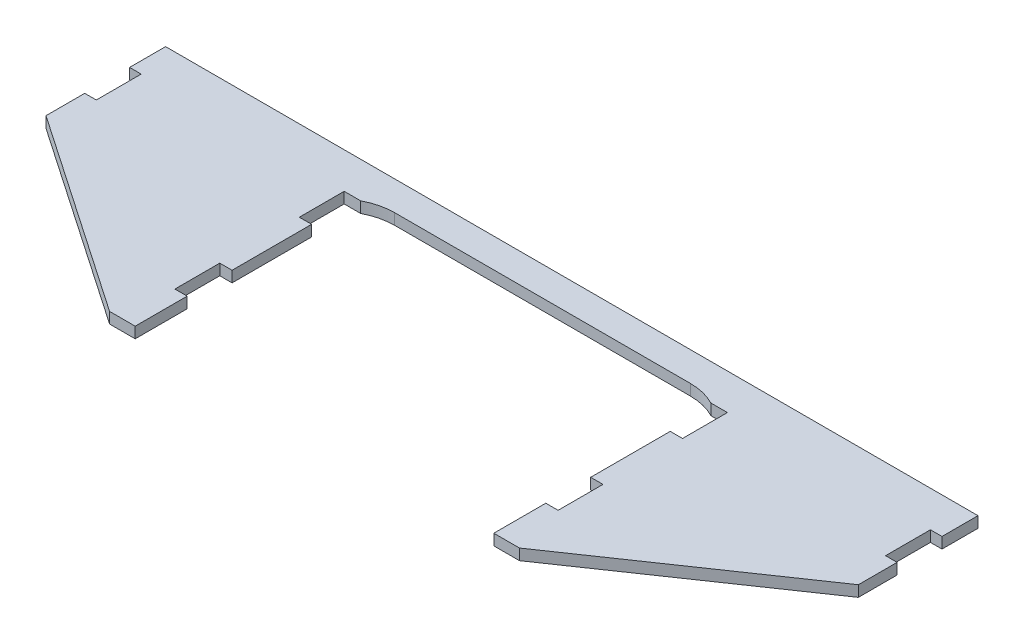
SolidWorks part; units mm, degrees
material "Plain Carbon Steel"
ref_plane "Front Plane" through (0, 0, 0) normal (0, 0, 1) x (1, 0, 0)
ref_plane "Top Plane" through (0, 0, 0) normal (0, 1, 0) x (1, 0, 0)
ref_plane "Right Plane" through (0, 0, 0) normal (1, 0, 0) x (0, 0, -1)
sketch "Sketch1" plane through (0, 0, 0) normal (0, 1, 0) x (1, 0, 0)
  line L0 (0, 25.4) -> (0, 0) construction
  line L1 (-177.8, 25.4) -> (177.8, 25.4)
  line L2 (-177.8, 25.4) -> (-177.8, -25.4)
  line L3 (-177.8, -25.4) -> (177.8, -25.4)
  line L4 (177.8, 25.4) -> (177.8, -25.4)
  line L5 (0, 0) -> (177.8, 0) construction
  dimension "D1" = 177.8
  dimension "D2" = 25.4
extrude "Boss-Extrude1" add sketch "Sketch1" along normal blind 4.7625
sketch "Sketch2" plane through (0, 4.7625, 0) normal (0, 1, 0) x (1, 0, 0)
  line L0 (177.8, -25.4) -> (88.9, -86.2204)
  line L1 (88.9, -86.2204) -> (76.2, -86.2204)
  line L2 (76.2, -86.2204) -> (76.2, -25.4)
  line L3 (-177.8, -25.4) -> (177.8, -25.4) construction
  line L4 (76.2, -25.4) -> (177.8, -25.4)
  line L5 (-177.8, -25.4) -> (-88.9, -86.2204)
  line L6 (-88.9, -86.2204) -> (-76.2, -86.2204)
  line L7 (-76.2, -86.2204) -> (-76.2, -25.4)
  line L8 (-76.2, -25.4) -> (-177.8, -25.4)
  line L9 (-88.9, -86.2204) -> (-76.2, -86.2204) construction
  line L10 (-76.2, -114.0491) -> (-76.2, -86.2204) construction
  line L11 (-88.9, 25.4) -> (-88.9, -86.2204) construction
extrude "Boss-Extrude2" add sketch "Sketch2" against normal blind 4.7625
sketch "Sketch3" plane through (0, 4.7625, 0) normal (0, 1, 0) x (1, 0, 0)
  line L0 (76.2, -25.4) -> (76.2, -86.2204) construction
  line L1 (82.55, -63.4133) -> (76.2, -63.4133)
  line L2 (82.55, -63.4133) -> (82.55, -44.45)
  line L3 (82.55, -44.45) -> (76.2, -44.45)
  line L4 (76.2, -63.4133) -> (76.2, -44.45)
  line L5 (177.8, -25.4) -> (177.8, 25.4) construction
  line L6 (171.45, -9.4383) -> (177.8, -9.4383)
  line L7 (171.45, -9.4383) -> (171.45, 9.525)
  line L8 (171.45, 9.525) -> (177.8, 9.525)
  line L9 (177.8, -9.4383) -> (177.8, 9.525)
  line L10 (-76.2, -86.2204) -> (-76.2, -25.4) construction
  line L11 (82.55, -9.4383) -> (76.2, -9.4383)
  line L12 (82.55, -9.4383) -> (82.55, 9.525)
  line L13 (82.55, 9.525) -> (76.2, 9.525)
  line L14 (76.2, -9.4383) -> (76.2, 9.525)
  line L15 (-82.55, -9.4383) -> (-76.2, -9.4383)
  line L16 (-82.55, -9.4383) -> (-82.55, 9.525)
  line L17 (-82.55, 9.525) -> (-76.2, 9.525)
  line L18 (-76.2, -9.4383) -> (-76.2, 9.525)
  line L19 (-82.55, -63.4133) -> (-76.2, -63.4133)
  line L20 (-82.55, -63.4133) -> (-82.55, -44.45)
  line L21 (-82.55, -44.45) -> (-76.2, -44.45)
  line L22 (-76.2, -63.4133) -> (-76.2, -44.45)
  line L23 (-177.8, 25.4) -> (-177.8, -25.4) construction
  line L24 (-171.45, -9.4383) -> (-177.8, -9.4383)
  line L25 (-171.45, -9.4383) -> (-171.45, 9.525)
  line L26 (-171.45, 9.525) -> (-177.8, 9.525)
  line L27 (-177.8, -9.4383) -> (-177.8, 9.525)
  line L28 (-171.196, -9.6923) -> (-171.196, 9.779)
  line L29 (-171.196, 9.779) -> (-178.054, 9.779)
  line L30 (-178.054, -9.6923) -> (-178.054, 9.779)
  line L31 (-171.196, -9.6923) -> (-178.054, -9.6923)
  line L32 (-82.804, -63.6673) -> (-82.804, -44.196)
  line L33 (-82.804, -44.196) -> (-75.946, -44.196)
  line L34 (-75.946, -63.6673) -> (-75.946, -44.196)
  line L35 (-82.804, -63.6673) -> (-75.946, -63.6673)
  line L36 (-82.804, -9.6923) -> (-82.804, 9.779)
  line L37 (-82.804, 9.779) -> (-75.946, 9.779)
  line L38 (-75.946, -9.6923) -> (-75.946, 9.779)
  line L39 (-82.804, -9.6923) -> (-75.946, -9.6923)
  line L40 (75.946, -9.6923) -> (75.946, 9.779)
  line L41 (82.804, 9.779) -> (75.946, 9.779)
  line L42 (82.804, -9.6923) -> (82.804, 9.779)
  line L43 (82.804, -9.6923) -> (75.946, -9.6923)
  line L44 (75.946, -63.6673) -> (75.946, -44.196)
  line L45 (82.804, -44.196) -> (75.946, -44.196)
  line L46 (82.804, -63.6673) -> (82.804, -44.196)
  line L47 (82.804, -63.6673) -> (75.946, -63.6673)
  line L48 (171.196, -9.6923) -> (171.196, 9.779)
  line L49 (171.196, 9.779) -> (178.054, 9.779)
  line L50 (178.054, -9.6923) -> (178.054, 9.779)
  line L51 (171.196, -9.6923) -> (178.054, -9.6923)
  dimension "D1" = 0.254
extrude "Cut-Extrude1" cut sketch "Sketch3" against normal through all
sketch "Sketch4" plane through (0, 4.7625, 0) normal (0, 1, 0) x (1, 0, 0)
  line L0 (-176.2125, 25.4) -> (-176.2125, -26.4861)
  line L1 (176.2125, 25.4) -> (176.2125, -26.4861)
  line L2 (77.7875, -63.6673) -> (77.7875, -86.2204)
  line L3 (-77.7875, -63.6673) -> (-77.7875, -86.2204)
  line L26 (177.8, -9.6923) -> (171.196, -9.6923)
  line L27 (171.196, -9.6923) -> (171.196, 9.779)
  line L28 (171.196, 9.779) -> (177.8, 9.779)
  line L29 (177.8, 9.779) -> (177.8, 25.4)
  line L30 (177.8, 25.4) -> (-177.8, 25.4)
  line L31 (-177.8, 25.4) -> (-177.8, 9.779)
  line L32 (-177.8, 9.779) -> (-171.196, 9.779)
  line L33 (-171.196, 9.779) -> (-171.196, -9.6923)
  line L34 (-171.196, -9.6923) -> (-177.8, -9.6923)
  line L35 (-177.8, -9.6923) -> (-177.8, -25.4)
  line L36 (-177.8, -25.4) -> (-88.9, -86.2204)
  line L37 (-88.9, -86.2204) -> (-76.2, -86.2204)
  line L38 (-76.2, -86.2204) -> (-76.2, -63.6673)
  line L39 (-76.2, -63.6673) -> (-82.804, -63.6673)
  line L40 (-82.804, -63.6673) -> (-82.804, -44.196)
  line L41 (-82.804, -44.196) -> (-76.2, -44.196)
  line L42 (-76.2, -44.196) -> (-76.2, -25.4)
  line L43 (-76.2, -25.4) -> (76.2, -25.4)
  line L44 (76.2, -25.4) -> (76.2, -44.196)
  line L45 (76.2, -44.196) -> (82.804, -44.196)
  line L46 (82.804, -44.196) -> (82.804, -63.6673)
  line L47 (82.804, -63.6673) -> (76.2, -63.6673)
  line L48 (76.2, -63.6673) -> (76.2, -86.2204)
  line L49 (76.2, -86.2204) -> (88.9, -86.2204)
  line L50 (88.9, -86.2204) -> (177.8, -25.4)
  line L51 (177.8, -25.4) -> (177.8, -9.6923)
  line L52 (177.8, -9.6923) -> (171.196, -9.6923)
  line L53 (171.196, -9.6923) -> (171.196, 9.779)
  line L54 (171.196, 9.779) -> (177.8, 9.779)
  line L55 (177.8, 9.779) -> (177.8, 25.4)
  line L56 (177.8, 25.4) -> (-177.8, 25.4)
  line L57 (-177.8, 25.4) -> (-177.8, 9.779)
  line L58 (-177.8, 9.779) -> (-171.196, 9.779)
  line L59 (-171.196, 9.779) -> (-171.196, -9.6923)
  line L60 (-171.196, -9.6923) -> (-177.8, -9.6923)
  line L61 (-177.8, -9.6923) -> (-177.8, -25.4)
  line L62 (-177.8, -25.4) -> (-88.9, -86.2204)
  line L63 (-88.9, -86.2204) -> (-76.2, -86.2204)
  line L64 (-76.2, -86.2204) -> (-76.2, -63.6673)
  line L65 (-76.2, -63.6673) -> (-82.804, -63.6673)
  line L66 (-82.804, -63.6673) -> (-82.804, -44.196)
  line L67 (-82.804, -44.196) -> (-76.2, -44.196)
  line L68 (-76.2, -44.196) -> (-76.2, -25.4)
  line L69 (-76.2, -25.4) -> (76.2, -25.4)
  line L70 (76.2, -25.4) -> (76.2, -44.196)
  line L71 (76.2, -44.196) -> (82.804, -44.196)
  line L72 (82.804, -44.196) -> (82.804, -63.6673)
  line L73 (82.804, -63.6673) -> (76.2, -63.6673)
  line L74 (76.2, -63.6673) -> (76.2, -86.2204)
  line L75 (76.2, -86.2204) -> (88.9, -86.2204)
  line L76 (88.9, -86.2204) -> (177.8, -25.4)
  line L77 (177.8, -25.4) -> (177.8, -9.6923)
  line M29 (177.8, -9.6923) -> (171.196, -9.6923)
  line M31 (171.196, 9.779) -> (177.8, 9.779)
  line M32 (177.8, 9.779) -> (177.8, 25.4)
  line M33 (177.8, 25.4) -> (-177.8, 25.4)
  line M34 (-177.8, 25.4) -> (-177.8, 9.779)
  line M35 (-177.8, 9.779) -> (-171.196, 9.779)
  line M37 (-171.196, -9.6923) -> (-177.8, -9.6923)
  line M38 (-177.8, -9.6923) -> (-177.8, -25.4)
  line M39 (-177.8, -25.4) -> (-88.9, -86.2204)
  line M40 (-88.9, -86.2204) -> (-76.2, -86.2204)
  line M41 (-76.2, -86.2204) -> (-76.2, -63.6673)
  line M42 (-76.2, -63.6673) -> (-82.804, -63.6673)
  line M52 (82.804, -63.6673) -> (76.2, -63.6673)
  line M53 (76.2, -63.6673) -> (76.2, -86.2204)
  line M54 (76.2, -86.2204) -> (88.9, -86.2204)
  line M55 (88.9, -86.2204) -> (177.8, -25.4)
  line M56 (177.8, -25.4) -> (177.8, -9.6923)
  dimension "D2" = 1.5875
  dimension "D3" = 1.5875
  dimension "D4" = 1.5875
  dimension "D5" = 1.5875
  dimension "D1" = 0
extrude "Cut-Extrude2" cut sketch "Sketch4" against normal through all contours L0 M37 M38 M39 | L0 M33 M34 M35 | L3 M42 M40 M41 | L2 M52 M53 M54 | L1 M29 M55 M56 | L1 M33 M31 M32 region at (-177.0062, 4.7625, -17.5895) region at (177.0062, 4.7625, -17.5895) region at (-176.9974, 4.7625, 17.8207) region at (176.9974, 4.7625, 17.8207) region at (-76.9937, 4.7625, 74.9439) region at (76.9938, 4.7625, 74.9439)
sketch "Sketch5" plane through (0, 4.7625, 0) normal (0, 1, 0) x (1, 0, 0)
  line L0 (176.2125, 25.4) -> (-176.2125, 25.4) construction
  line L1 (-76.2, -25.4) -> (76.2, -25.4)
  line L2 (-76.2, -25.4) -> (-76.2, 12.7)
  line L3 (-76.2, 12.7) -> (76.2, 12.7)
  line L4 (76.2, -25.4) -> (76.2, 12.7)
  arc A0 (-75.946, 9.779) -> (-64.12, 12.7) centre (-64.12, -12.7) cw
  arc A1 (75.946, 9.779) -> (64.12, 12.7) centre (64.12, -12.7) ccw
  line M19 (-76.2, -25.4) -> (76.2, -25.4)
  line M31 (-75.946, -9.6923) -> (-82.804, -9.6923)
  line M33 (-82.804, 9.779) -> (-75.946, 9.779)
  line M34 (-75.946, 9.779) -> (-75.946, -9.6923)
  line M35 (82.804, -9.6923) -> (75.946, -9.6923)
  line M36 (75.946, -9.6923) -> (75.946, 9.779)
  line M37 (75.946, 9.779) -> (82.804, 9.779)
  dimension "D2" = 25.4
  dimension "D1" = 12.7
extrude "Cut-Extrude3" cut sketch "Sketch5" against normal through all contours L4 L3 L2 M19 M35 M36 M37 M33 M34 M31 region at (0, 4.7625, 6.4363)
sketch "Sketch6" plane through (0, 4.7625, 0) normal (0, 1, 0) x (1, 0, 0)
  line L0 (-82.804, -63.6673) -> (-77.7875, -63.6673) construction
  line L1 (-82.804, 9.779) -> (-83.1215, 9.779)
  line L2 (-82.804, 9.779) -> (-82.804, -9.6923)
  line L3 (-82.804, -9.6923) -> (-83.1215, -9.6923)
  line L4 (-83.1215, 9.779) -> (-83.1215, -9.6923)
  line L5 (-82.804, -44.196) -> (-83.1215, -44.196)
  line L6 (-82.804, -44.196) -> (-82.804, -63.6673)
  line L7 (-82.804, -63.6673) -> (-83.1215, -63.6673)
  line L8 (-83.1215, -44.196) -> (-83.1215, -63.6673)
  line L9 (82.804, -63.6673) -> (83.1215, -63.6673)
  line L10 (82.804, -63.6673) -> (82.804, -44.196)
  line L11 (82.804, -44.196) -> (83.1215, -44.196)
  line L12 (83.1215, -63.6673) -> (83.1215, -44.196)
  line L13 (82.804, -9.6923) -> (83.1215, -9.6923)
  line L14 (82.804, -9.6923) -> (82.804, 9.779)
  line L15 (82.804, 9.779) -> (83.1215, 9.779)
  line L16 (83.1215, -9.6923) -> (83.1215, 9.779)
  dimension "D1" = 166.243
extrude "Cut-Extrude4" cut sketch "Sketch6" against normal through all
sketch "Sketch7" plane through (0, 4.7625, 0) normal (0, 1, 0) x (1, 0, 0)
  line L0 (76.2, -9.6923) -> (83.1215, -9.6923) construction
  line L1 (-77.7875, -86.2204) -> (77.7875, -86.2204)
  line L2 (-77.7875, -86.2204) -> (-77.7875, -9.6923)
  line L3 (-77.7875, -9.6923) -> (77.7875, -9.6923)
  line L4 (77.7875, -86.2204) -> (77.7875, -9.6923)
extrude "Cut-Extrude5" cut sketch "Sketch7" against normal through all
